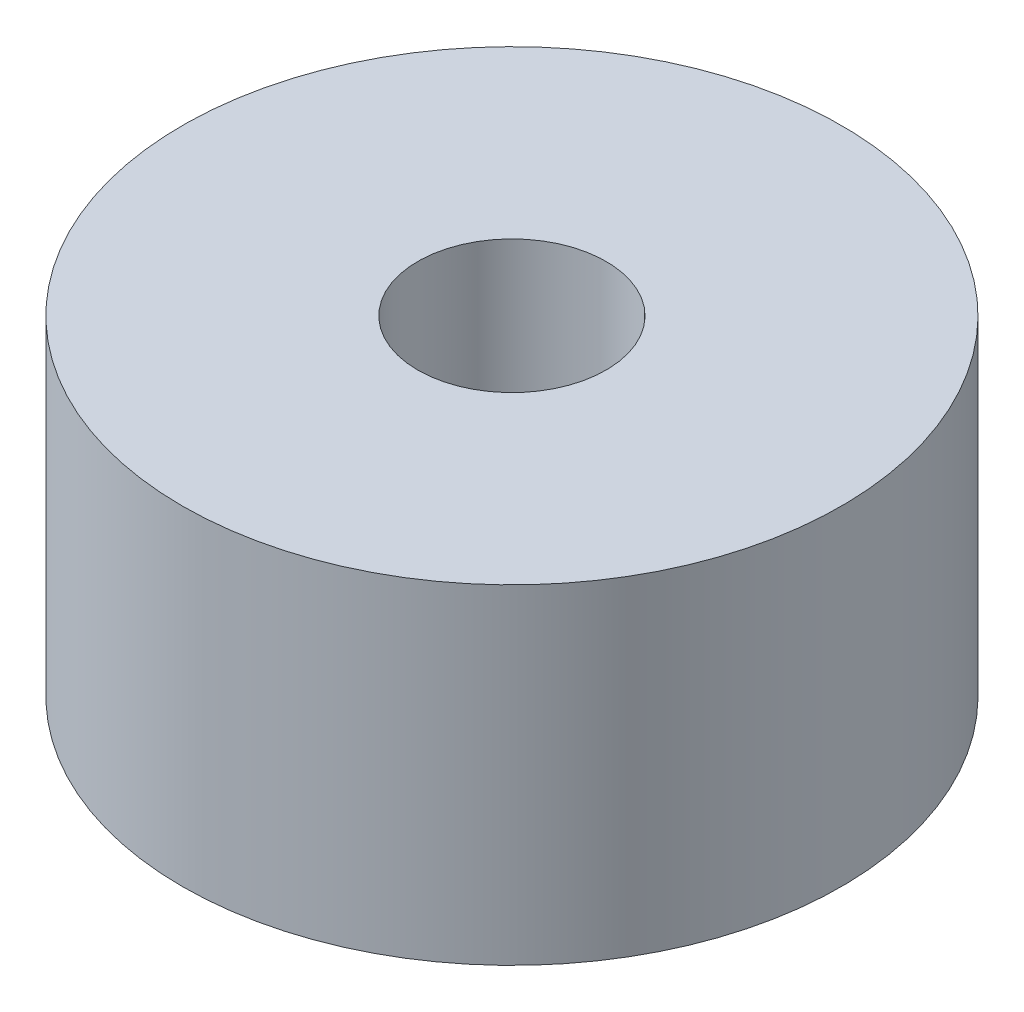
SolidWorks part; units mm, degrees
ref_plane "Front Plane" through (0, 0, 0) normal (0, 0, 1) x (1, 0, 0)
ref_plane "Top Plane" through (0, 0, 0) normal (0, 1, 0) x (1, 0, 0)
ref_plane "Right Plane" through (0, 0, 0) normal (1, 0, 0) x (0, 0, -1)
sketch "Sketch1" plane through (0, 0, 0) normal (0, 1, 0) x (1, 0, 0)
  circle A0 centre (0, 0) radius 30 construction
  circle A1 centre (0, 0) radius 35 construction
  circle A2 centre (0, 0) radius 25 construction
  circle A6 centre (0, 0) radius 10
  circle A7 centre (0, 0) radius 35
  dimension "D2" = 70
  dimension "D6" = 20
extrude "Boss-Extrude1" add sketch "Sketch1" along normal blind 35
